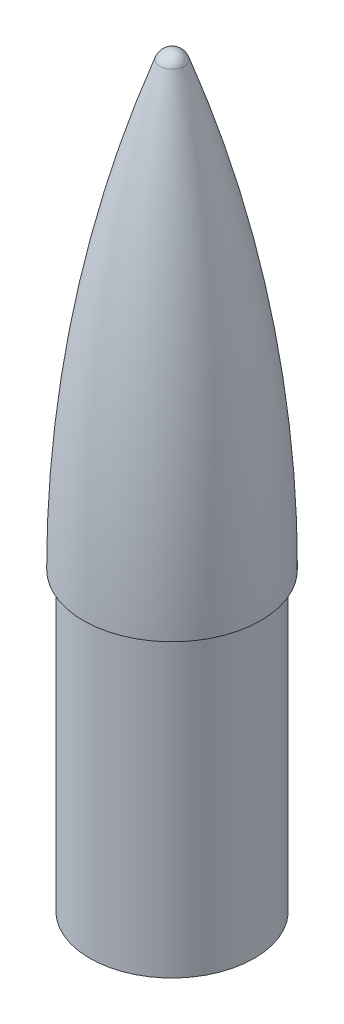
SolidWorks part; units mm, degrees
material "PLA"
ref_plane "Front Plane" through (0, 0, 0) normal (0, 0, 1) x (1, 0, 0)
ref_plane "Top Plane" through (0, 0, 0) normal (0, 1, 0) x (1, 0, 0)
ref_plane "Right Plane" through (0, 0, 0) normal (1, 0, 0) x (0, 0, -1)
sketch "Sketch1" plane through (0, 0, 0) normal (0, 0, 1) x (1, 0, 0)
  line L0 (-20.555, 0) -> (-20.555, -8.881) construction
  line L1 (-19.055, 0) -> (-20.555, 0)
  line L2 (0, 102.3969) -> (0, 104.3969)
  line L3 (0, 110) -> (-20.555, 110) construction
  line L4 (-20.555, 0) -> (-20.555, 110) construction
  line L6 (0, 0) -> (0, -68.5545) construction
  line L7 (-17.055, -68.5545) -> (-19.055, -68.5545)
  line L8 (-19.055, 0) -> (-19.055, -68.5545)
  line L9 (-17.055, 2) -> (-17.055, -68.5545) construction
  line L10 (-17.055, 2) -> (-18.5484, 2) construction
  line L11 (0, -68.5545) -> (-17.055, -68.5545) construction
  line L12 (0, 0) -> (0, 102.3969) construction
  line L13 (-10, 71.4455) -> (-10, -68.5545)
  line L14 (-17.055, -68.5545) -> (-10, -68.5545)
  line L15 (-10, 71.4455) -> (0, 71.4455)
  line L16 (0, 71.4455) -> (0, 102.3969)
  arc A0 (-20.555, 0) -> (-2.8254, 102.4055) centre (284.0548, 0) cw
  arc A1 (0, 104.3969) -> (-2.8254, 102.4055) centre (0, 101.3969) ccw
  arc A2 (-10, 71.4455) -> (-0.9418, 101.7331) centre (284.0548, 0) cw construction
  arc A3 (0, 102.3969) -> (-0.9418, 101.7331) centre (0, 101.3969) ccw construction
  arc A4 (-20.555, 0) -> (61.9638, 208.4772) centre (284.0548, 0) cw
  arc A5 (-18.5484, 2) -> (-10, 71.4455) centre (284.0548, 0) cw construction
  arc A6 (-18.5484, 2) -> (-0.9418, 101.7331) centre (284.0548, 0) cw construction
  dimension "D5" = 6
  dimension "D1" = 110
  dimension "D2" = 20.555
  dimension "D4" = 1.5
  dimension "D7" = 10
  dimension "D8" = 140
  dimension "D6" = 2
revolve "Revolve3" add sketch "Sketch1" angle 360 about L2 region at (-12.669, 10.8541, 0)
sketch "Sketch2" plane through (0, -68.5545, 0) normal (0, -1, 0) x (1, 0, 0)
  circle A0 centre (0, -14.055) radius 2.35
  circle A2 centre (0, 14.055) radius 2.35
  point P7 (0, 0)
  dimension "D1" = 4.7
  dimension "D3" = 2
  dimension "D2" = 14.055
extrude "Cut-Extrude1" cut sketch "Sketch2" against normal blind 10
